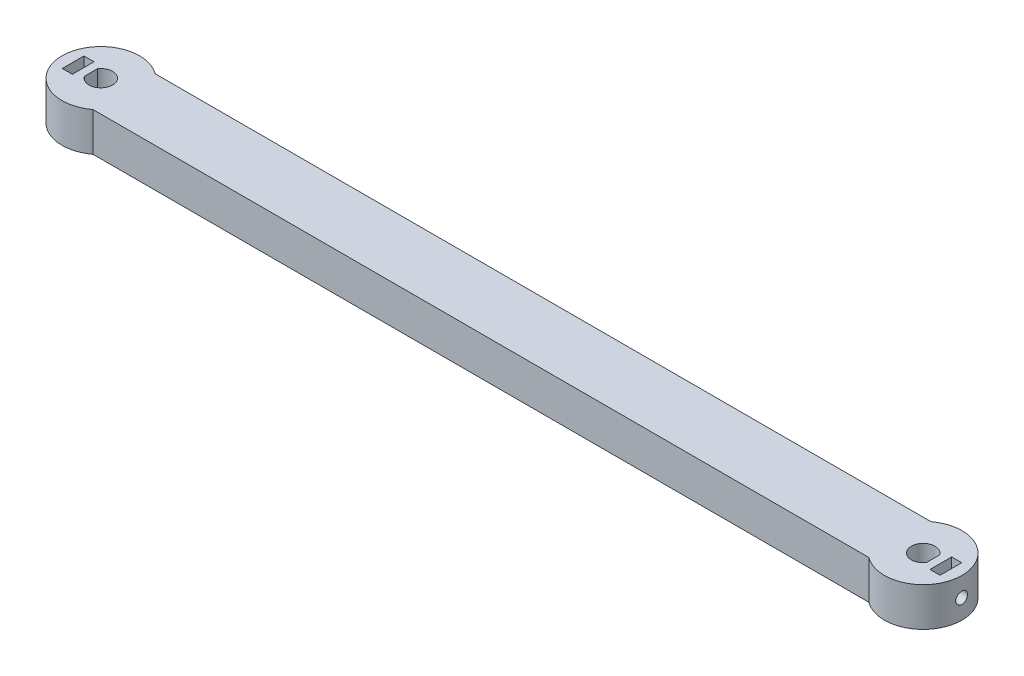
SolidWorks part; units mm, degrees
ref_plane "Plano frontal" through (0, 0, 0) normal (0, 0, 1) x (1, 0, 0)
ref_plane "Plano superior" through (0, 0, 0) normal (0, 1, 0) x (1, 0, 0)
ref_plane "Plano direito" through (0, 0, 0) normal (1, 0, 0) x (0, 0, -1)
sketch "Esboço1" plane through (0, 0, 0) normal (0, 1, 0) x (1, 0, 0)
  line L2 (6, 8) -> (206, 8)
  line L3 (6, -8) -> (206, -8)
  line L6 (-3.7598, 0) -> (4.2446, 0) construction
  line L8 (106, 14.4945) -> (106, -12.8649) construction
  arc A4 (6, 8) -> (6, -8) centre (0, 0) ccw
  arc A5 (206, -8) -> (206, 8) centre (212, 0) ccw
  dimension "D2" = 20
  dimension "D3" = 20
  dimension "D4" = 200
  dimension "D7" = 8
  dimension "D8" = 8
extrude "Ressalto-extrusão1" add sketch "Esboço1" along normal blind 10
sketch "Esboço2" plane through (0, 10, 0) normal (0, 1, 0) x (1, 0, 0)
  line L0 (-11.6519, 0) -> (19.7902, 0) construction
  line L1 (-2.5417, 1.6858) -> (-2.5417, -1.6858)
  line L2 (-2.5417, 1.6858) -> (0, 0) construction
  line L3 (0, 0) -> (-2.5417, -1.6858) construction
  line L4 (106, 17.1389) -> (106, -14.6242) construction
  line L6 (214.5417, 1.6858) -> (214.5417, -1.6858)
  arc A0 (-2.5417, -1.6858) -> (-2.5417, 1.6858) centre (0, 0) ccw
  arc A2 (214.5417, -1.6858) -> (214.5417, 1.6858) centre (212, 0) cw
  dimension "D1" = 3.05
  dimension "D2" = 67.11
extrude "Corte-extrusão1" cut sketch "Esboço2" against normal up to surface (10 mm away) up to face at (106, 0, 0)
sketch "Esboço3" plane through (-2.5417, 0, 0) normal (1, 0, 0) x (0, 0, -1)
  line L0 (1.6858, 5) -> (-1.6858, 5) construction
  line L1 (1.6858, 0) -> (1.6858, 10) construction
  line L2 (-1.6858, 0) -> (-1.6858, 10) construction
  line L3 (-1.6858, 0) -> (1.6858, 0) construction
  circle A0 centre (0, 5) radius 1.5
  point P11 (0, 0)
  dimension "D1" = 3
extrude "Corte-extrusão2" cut sketch "Esboço3" against normal through all
sketch "Esboço4" plane through (214.5417, 0, 0) normal (-1, 0, 0) x (0, 0, 1)
  line L3 (1.6858, 0) -> (1.6858, 10) construction
  line L4 (-1.6858, 0) -> (1.6858, 0) construction
  circle A0 centre (0, 5) radius 1.5
  point P4 (1.6858, 5)
  point P7 (0, 0)
  dimension "D1" = 3
extrude "Corte-extrusão3" cut sketch "Esboço4" against normal through all
sketch "Esboço5" plane through (0, 10, 0) normal (0, 1, 0) x (1, 0, 0)
  line L0 (-2.5417, 1.6858) -> (-2.5417, -1.6858) construction
  line L1 (-7.1417, 2.8) -> (-4.5417, 2.8)
  line L2 (-7.1417, 2.8) -> (-7.1417, -2.8)
  line L3 (-7.1417, -2.8) -> (-4.5417, -2.8)
  line L4 (-4.5417, 2.8) -> (-4.5417, -2.8)
  line L5 (106, 15.5807) -> (106, -13.2968) construction
  line L10 (219.1417, -2.8) -> (216.5417, -2.8)
  line L11 (216.5417, 2.8) -> (216.5417, -2.8)
  line L12 (219.1417, 2.8) -> (219.1417, -2.8)
  line L13 (219.1417, 2.8) -> (216.5417, 2.8)
  point P4 (-7.1417, 0)
  dimension "D1" = 2.6
  dimension "D2" = 5.6
  dimension "D3" = 2
extrude "Corte-extrusão4" cut sketch "Esboço5" against normal blind 5
sketch "Esboço6" plane through (-2.5417, 0, 0) normal (1, 0, 0) x (0, 0, -1)
  line L0 (1.6858, 0) -> (1.6858, 10) construction
  line L1 (0, 8.2332) -> (-2.8, 6.6166)
  line L2 (-2.8, 6.6166) -> (-2.8, 3.3834)
  line L3 (-2.8, 3.3834) -> (0, 1.7668)
  line L4 (0, 1.7668) -> (2.8, 3.3834)
  line L5 (2.8, 3.3834) -> (2.8, 6.6166)
  line L6 (2.8, 6.6166) -> (0, 8.2332)
  line L7 (-1.6858, 0) -> (-1.6858, 10) construction
  circle A0 centre (0, 5) radius 2.8 construction
  point P11 (1.6858, 5)
  dimension "D1" = 5.6
extrude "Corte-extrusão5" cut sketch "Esboço6" against normal blind 2.6 from offset 2 offset against normal yes
sketch "Esboço7" plane through (214.5417, 0, 0) normal (-1, 0, 0) x (0, 0, 1)
  line L1 (0, 8.2332) -> (-2.8, 6.6166)
  line L2 (-2.8, 6.6166) -> (-2.8, 3.3834)
  line L3 (-2.8, 3.3834) -> (0, 1.7668)
  line L4 (0, 1.7668) -> (2.8, 3.3834)
  line L5 (2.8, 3.3834) -> (2.8, 6.6166)
  line L6 (2.8, 6.6166) -> (0, 8.2332)
  line L8 (-1.6858, 0) -> (-1.6858, 10) construction
  circle A0 centre (0, 5) radius 2.8 construction
  point P10 (0, 0)
  dimension "D1" = 5.6
extrude "Corte-extrusão6" cut sketch "Esboço7" against normal blind 2.6 from offset 2 offset against normal yes
